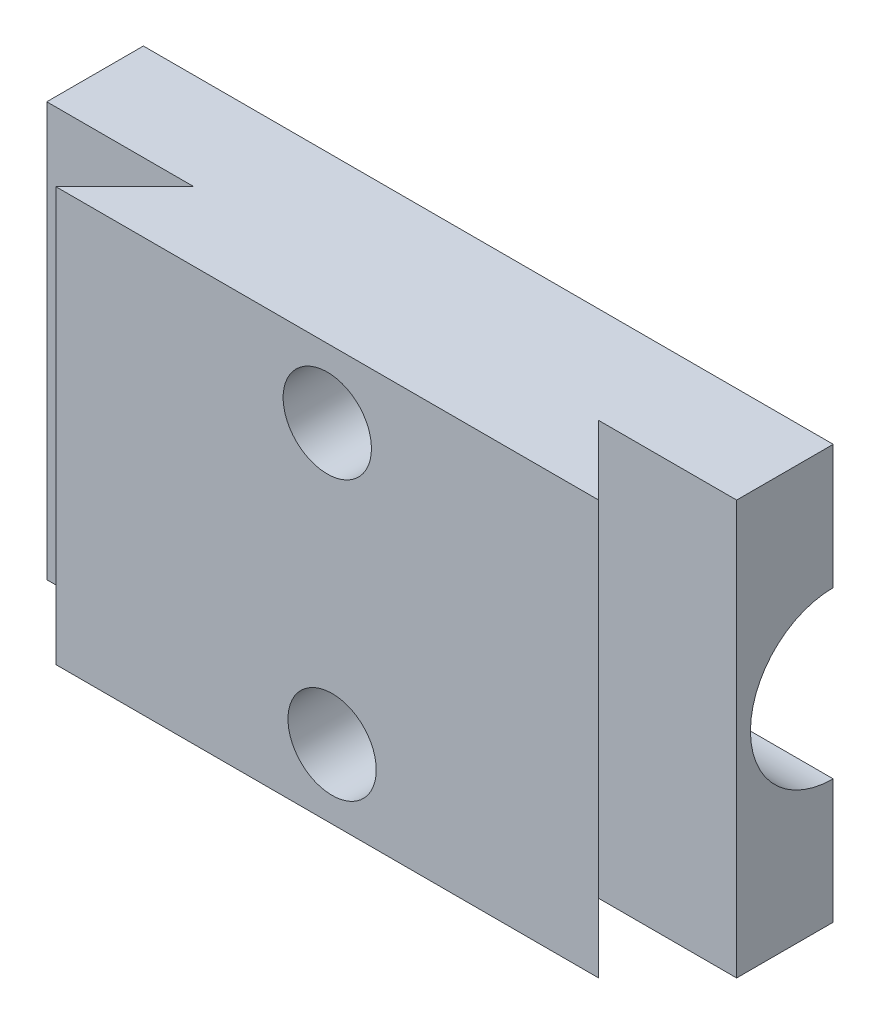
SolidWorks part; units mm, degrees
material "ABS"
ref_plane "Спереди" through (0, 0, 0) normal (0, 0, 1) x (1, 0, 0)
ref_plane "Сверху" through (0, 0, 0) normal (0, 1, 0) x (1, 0, 0)
ref_plane "Справа" through (0, 0, 0) normal (1, 0, 0) x (0, 0, -1)
sketch "Эскиз1" plane through (0, 0, 0) normal (0, 0, 1) x (1, 0, 0)
  line L1 (50, 0) -> (0, 0)
  line L2 (50, 0) -> (50, 30)
  line L3 (50, 30) -> (0, 30)
  line L4 (0, 0) -> (0, 30)
extrude "основание" add sketch "Эскиз1" along normal mid plane 10
sketch "Эскиз2" plane through (0, 30, 0) normal (0, 1, 0) x (1, 0, 0)
  line L0 (0, 0) -> (10.6623, 0)
  line L1 (10.6623, 0) -> (5.6623, -5)
  line L2 (50, -5) -> (0, -5) construction
  line L4 (50, 0) -> (40, 0)
  line L5 (50, -5) -> (50, 5) construction
  line L6 (40, 0) -> (45, -5)
  line M2 (0, 5) -> (0, -5)
  line M3 (0, -5) -> (50, -5)
  line M4 (50, -5) -> (50, 5)
extrude "Ластахвост" cut sketch "Эскиз2" against normal through all contours L1 L0 M2 M3 | L4 L6 M3 M4 region at (46.1111, 30, 2.2222) region at (4.2088, 30, 2.2448)
sketch "Эскиз8" plane through (0, 0, -5) normal (0, 0, -1) x (-1, 0, 0)
  line L1 (-50, 0) -> (0, 0)
  line L2 (-50, 0) -> (-50, 30)
  line L3 (-50, 30) -> (0, 30)
  line L4 (0, 0) -> (0, 30)
extrude "Бобышка-Вытянуть1" add sketch "Эскиз8" along normal blind 2
sketch "Эскиз11" plane through (0, 0, 0) normal (-1, 0, 0) x (0, 0, 1)
  line L0 (-7, 0) -> (-7, 30) construction
  circle A0 centre (-7, 15) radius 6
extrude "Вырез-Вытянуть2" cut sketch "Эскиз11" against normal through all
sketch "Эскиз12" plane through (0, 0, 5) normal (0, 0, 1) x (1, 0, 0)
  circle A0 centre (25.6799, 5) radius 1.5
  circle A1 centre (25.3311, 25) radius 1.5
  circle A2 centre (25.3311, 25) radius 3.2
  circle A3 centre (25.6799, 5) radius 3.2
extrude "Вырез-Вытянуть3" cut sketch "Эскиз12" against normal through all contours A1 | A0
extrude "Вырез-Вытянуть4" cut sketch "Эскиз12<3>" against normal blind 5 contours A2 | A3
sketch "Эскиз12<3>" plane through (0, 0, 5) normal (0, 0, 1) x (1, 0, 0) same geometry as "Эскиз12"
